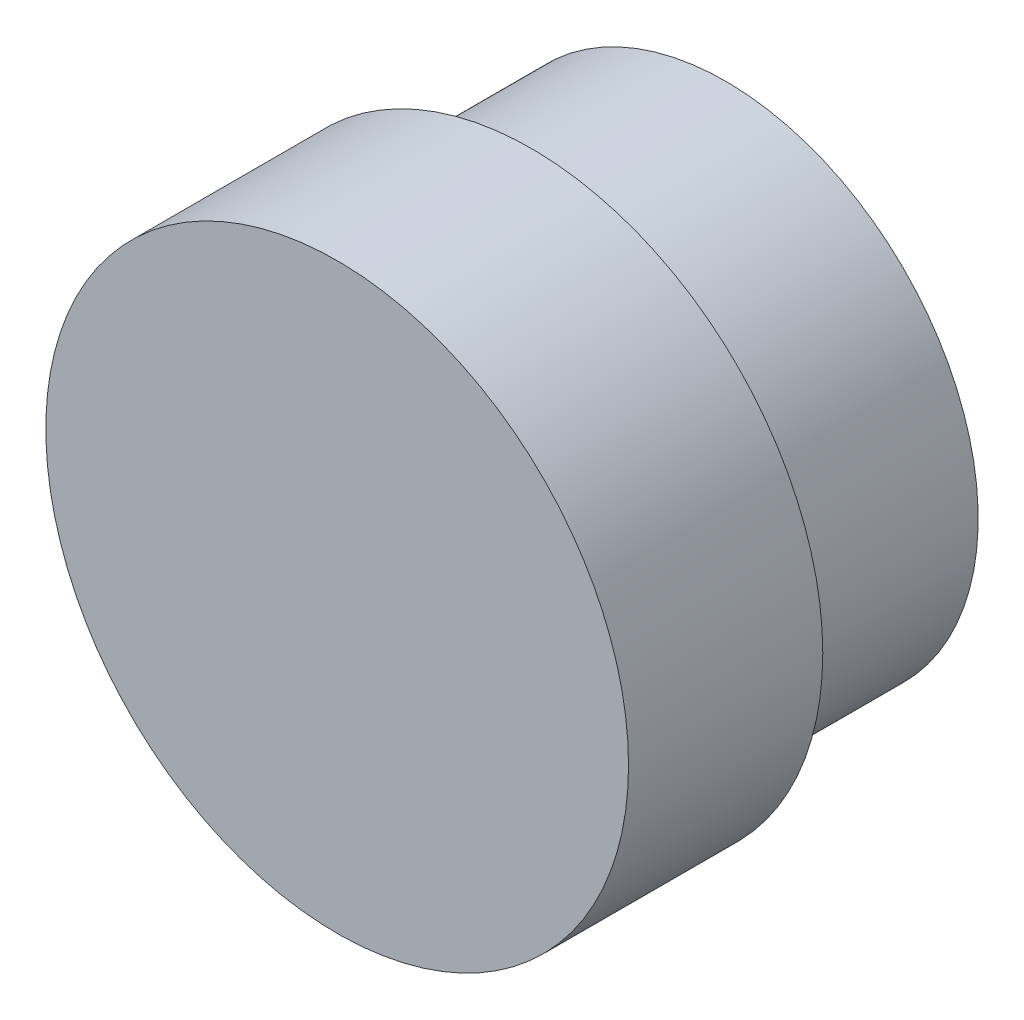
SolidWorks part; units mm, degrees
ref_plane "正面" through (0, 0, 0) normal (0, 0, 1) x (1, 0, 0)
ref_plane "平面" through (0, 0, 0) normal (0, 1, 0) x (1, 0, 0)
ref_plane "右側面" through (0, 0, 0) normal (1, 0, 0) x (0, 0, -1)
sketch "ｽｹｯﾁ5" plane through (0, 0, 0) normal (0, 1, 0) x (1, 0, 0)
  line L0 (0, -50) -> (0, -55)
  line L1 (-6.5, -55) -> (6.5, -55)
  line L2 (-6.5, -55) -> (-6.5, -50)
  line L3 (-6.5, -50) -> (6.5, -50)
  line L4 (6.5, -55) -> (6.5, -50)
  line L5 (-6.5, -55) -> (6.5, -50) construction
  line L6 (-6.5, -50) -> (6.5, -55) construction
  point P0 (0, -52.5)
  dimension "D1" = 52.5
  dimension "D2" = 13
  dimension "D3" = 5
revolve "回転4" add sketch "ｽｹｯﾁ5" angle 360 about L0 region at (-3.25, 0, 52.5)
sketch "ｽｹｯﾁ7" plane through (0, 0, 0) normal (0, 1, 0) x (1, 0, 0)
  line L0 (0, -60) -> (0, -55) construction
  line L1 (-7.5, -60) -> (7.5, -60)
  line L2 (-7.5, -60) -> (-7.5, -55)
  line L3 (-7.5, -55) -> (7.5, -55)
  line L4 (7.5, -60) -> (7.5, -55)
  point P0 (0, -57.5)
  dimension "D1" = 57.5
  dimension "D2" = 5
  dimension "D3" = 15
revolve "回転5" add sketch "ｽｹｯﾁ7" angle 360 about L0 region at (3.75, 0, 57.5)
